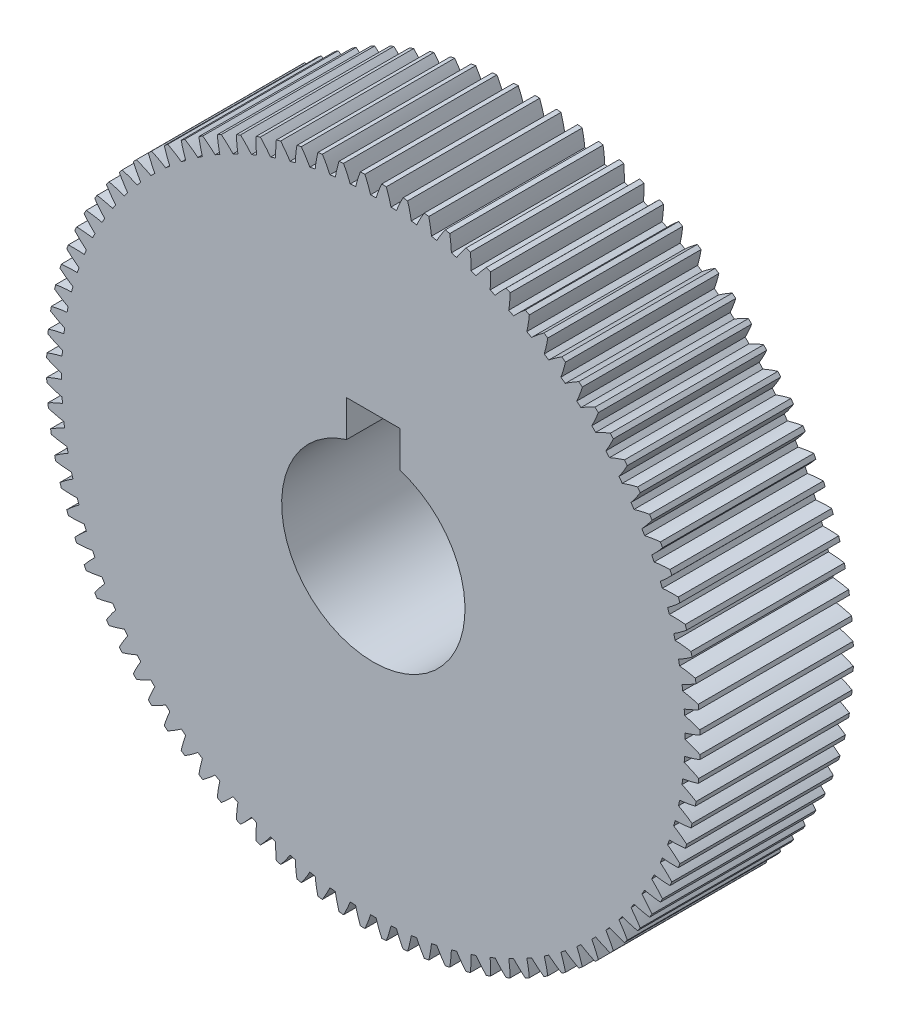
SolidWorks part; units mm, degrees
ref_plane "前视基准面" through (0, 0, 0) normal (0, 0, 1) x (1, 0, 0)
ref_plane "上视基准面" through (0, 0, 0) normal (0, 1, 0) x (1, 0, 0)
ref_plane "右视基准面" through (0, 0, 0) normal (1, 0, 0) x (0, 0, -1)
sketch "Model" plane through (0, 0, 0) normal (0, 0, 1) x (1, 0, 0)
  line L0 (6, 19.0788) -> (6, 23.3)
  line L1 (-6, 23.3) -> (-6, 19.0788)
  line L2 (6, 23.3) -> (-6, 23.3)
  arc A0 (-97.9675, 2.5241) -> (-93.4954, 0.8163) centre (-82.0589, 37.4737) ccw
  arc A1 (-93.4954, 0.8163) -> (-93.4954, -0.8163) centre (0, 0) ccw
  arc A2 (-93.4954, -0.8163) -> (-97.9675, -2.5241) centre (-82.0589, -37.4737) ccw
  arc A3 (-97.9675, -2.5241) -> (-97.9228, -3.8887) centre (0, 0) ccw
  arc A4 (-97.9228, -3.8887) -> (-93.3486, -5.3003) centre (-84.3341, 32.0266) ccw
  arc A5 (-93.3486, -5.3003) -> (-93.2419, -6.9294) centre (0, 0) ccw
  arc A6 (-93.2419, -6.9294) -> (-97.5927, -8.9261) centre (-79.4323, -42.7604) ccw
  arc A7 (-97.5927, -8.9261) -> (-97.4588, -10.2848) centre (0, 0) ccw
  arc A8 (-97.4588, -10.2848) -> (-92.8021, -11.3943) centre (-86.2481, 26.4423) ccw
  arc A9 (-92.8021, -11.3943) -> (-92.589, -13.0129) centre (0, 0) ccw
  arc A10 (-92.589, -13.0129) -> (-96.7999, -15.2898) centre (-76.4655, -47.8639) ccw
  arc A11 (-96.7999, -15.2898) -> (-96.5775, -16.6369) centre (0, 0) ccw
  arc A12 (-96.5775, -16.6369) -> (-91.8582, -17.4394) centre (-87.7929, 20.7448) ccw
  arc A13 (-91.8582, -17.4394) -> (-91.5397, -19.0407) centre (0, 0) ccw
  arc A14 (-91.5397, -19.0407) -> (-95.5926, -21.5881) centre (-73.1714, -52.7625) ccw
  arc A15 (-95.5926, -21.5881) -> (-95.2826, -22.9178) centre (0, 0) ccw
  arc A16 (-95.2826, -22.9178) -> (-90.5209, -23.4099) centre (-88.9617, 14.9584) ccw
  arc A17 (-90.5209, -23.4099) -> (-90.0984, -24.9869) centre (0, 0) ccw
  arc A18 (-90.0984, -24.9869) -> (-93.976, -27.7939) centre (-69.5639, -57.4352) ccw
  arc A19 (-93.976, -27.7939) -> (-93.5797, -29.1005) centre (0, 0) ccw
  arc A20 (-93.5797, -29.1005) -> (-88.796, -29.2801) centre (-89.7495, 9.108) ccw
  arc A21 (-88.796, -29.2801) -> (-88.2713, -30.8261) centre (0, 0) ccw
  arc A22 (-88.2713, -30.8261) -> (-91.957, -33.8808) centre (-65.6585, -61.8619) ccw
  arc A23 (-91.957, -33.8808) -> (-91.4761, -35.1586) centre (0, 0) ccw
  arc A24 (-91.4761, -35.1586) -> (-86.6909, -35.025) centre (-90.1531, 3.2186) ccw
  arc A25 (-86.6909, -35.025) -> (-86.0661, -36.5333) centre (0, 0) ccw
  arc A26 (-86.0661, -36.5333) -> (-89.5442, -39.8225) centre (-61.4719, -66.0237) ccw
  arc A27 (-89.5442, -39.8225) -> (-88.9807, -41.0661) centre (0, 0) ccw
  arc A28 (-88.9807, -41.0661) -> (-84.2145, -40.6199) centre (-90.1705, -2.6846) ccw
  arc A29 (-84.2145, -40.6199) -> (-83.4925, -42.0841) centre (0, 0) ccw
  arc A30 (-83.4925, -42.0841) -> (-86.748, -45.5937) centre (-57.0222, -69.9028) ccw
  arc A31 (-86.748, -45.5937) -> (-86.1044, -46.7978) centre (0, 0) ccw
  arc A32 (-86.1044, -46.7978) -> (-81.3776, -46.0408) centre (-89.8019, -8.5763) ccw
  arc A33 (-81.3776, -46.0408) -> (-80.5613, -47.4547) centre (0, 0) ccw
  arc A34 (-80.5613, -47.4547) -> (-83.5803, -51.1697) centre (-52.3282, -73.4826) ccw
  arc A35 (-83.5803, -51.1697) -> (-82.8593, -52.3291) centre (0, 0) ccw
  arc A36 (-82.8593, -52.3291) -> (-78.1921, -51.2646) centre (-89.0487, -14.4312) ccw
  arc A37 (-78.1921, -51.2646) -> (-77.2851, -52.622) centre (0, 0) ccw
  arc A38 (-77.2851, -52.622) -> (-80.0547, -56.5265) centre (-47.4102, -76.7477) ccw
  arc A39 (-80.0547, -56.5265) -> (-79.2594, -57.6363) centre (0, 0) ccw
  arc A40 (-79.2594, -57.6363) -> (-74.6719, -56.2688) centre (-87.9142, -20.2244) ccw
  arc A41 (-74.6719, -56.2688) -> (-73.678, -57.564) centre (0, 0) ccw
  arc A42 (-73.678, -57.564) -> (-76.1863, -61.6413) centre (-42.2891, -79.6841) ccw
  arc A43 (-76.1863, -61.6413) -> (-75.3201, -62.6967) centre (0, 0) ccw
  arc A44 (-75.3201, -62.6967) -> (-70.8318, -61.0321) centre (-86.4032, -25.9309) ccw
  arc A45 (-70.8318, -61.0321) -> (-69.7554, -62.2596) centre (0, 0) ccw
  arc A46 (-69.7554, -62.2596) -> (-71.9916, -66.4922) centre (-36.987, -82.2794) ccw
  arc A47 (-71.9916, -66.4922) -> (-71.0583, -67.4887) centre (0, 0) ccw
  arc A48 (-71.0583, -67.4887) -> (-66.6885, -65.534) centre (-84.5223, -31.5265) ccw
  arc A49 (-66.6885, -65.534) -> (-65.534, -66.6885) centre (0, 0) ccw
  arc A50 (-65.534, -66.6885) -> (-67.4887, -71.0583) centre (-31.5265, -84.5223) ccw
  arc A51 (-67.4887, -71.0583) -> (-66.4922, -71.9916) centre (0, 0) ccw
  arc A52 (-66.4922, -71.9916) -> (-62.2596, -69.7554) centre (-82.2794, -36.987) ccw
  arc A53 (-62.2596, -69.7554) -> (-61.0321, -70.8318) centre (0, 0) ccw
  arc A54 (-61.0321, -70.8318) -> (-62.6967, -75.3201) centre (-25.9309, -86.4032) ccw
  arc A55 (-62.6967, -75.3201) -> (-61.6413, -76.1863) centre (0, 0) ccw
  arc A56 (-61.6413, -76.1863) -> (-57.564, -73.678) centre (-79.6841, -42.2891) ccw
  arc A57 (-57.564, -73.678) -> (-56.2688, -74.6719) centre (0, 0) ccw
  arc A58 (-56.2688, -74.6719) -> (-57.6363, -79.2594) centre (-20.2244, -87.9142) ccw
  arc A59 (-57.6363, -79.2594) -> (-56.5265, -80.0547) centre (0, 0) ccw
  arc A60 (-56.5265, -80.0547) -> (-52.622, -77.2851) centre (-76.7477, -47.4102) ccw
  arc A61 (-52.622, -77.2851) -> (-51.2646, -78.1921) centre (0, 0) ccw
  arc A62 (-51.2646, -78.1921) -> (-52.3291, -82.8593) centre (-14.4312, -89.0487) ccw
  arc A63 (-52.3291, -82.8593) -> (-51.1697, -83.5803) centre (0, 0) ccw
  arc A64 (-51.1697, -83.5803) -> (-47.4547, -80.5613) centre (-73.4826, -52.3282) ccw
  arc A65 (-47.4547, -80.5613) -> (-46.0408, -81.3776) centre (0, 0) ccw
  arc A66 (-46.0408, -81.3776) -> (-46.7978, -86.1044) centre (-8.5763, -89.8019) ccw
  arc A67 (-46.7978, -86.1044) -> (-45.5937, -86.748) centre (0, 0) ccw
  arc A68 (-45.5937, -86.748) -> (-42.0841, -83.4925) centre (-69.9028, -57.0222) ccw
  arc A69 (-42.0841, -83.4925) -> (-40.6199, -84.2145) centre (0, 0) ccw
  arc A70 (-40.6199, -84.2145) -> (-41.0661, -88.9807) centre (-2.6846, -90.1705) ccw
  arc A71 (-41.0661, -88.9807) -> (-39.8225, -89.5442) centre (0, 0) ccw
  arc A72 (-39.8225, -89.5442) -> (-36.5333, -86.0661) centre (-66.0237, -61.4719) ccw
  arc A73 (-36.5333, -86.0661) -> (-35.025, -86.6909) centre (0, 0) ccw
  arc A74 (-35.025, -86.6909) -> (-35.1586, -91.4761) centre (3.2186, -90.1531) ccw
  arc A75 (-35.1586, -91.4761) -> (-33.8808, -91.957) centre (0, 0) ccw
  arc A76 (-33.8808, -91.957) -> (-30.8261, -88.2713) centre (-61.8619, -65.6585) ccw
  arc A77 (-30.8261, -88.2713) -> (-29.2801, -88.796) centre (0, 0) ccw
  arc A78 (-29.2801, -88.796) -> (-29.1005, -93.5797) centre (9.108, -89.7495) ccw
  arc A79 (-29.1005, -93.5797) -> (-27.7939, -93.976) centre (0, 0) ccw
  arc A80 (-27.7939, -93.976) -> (-24.9869, -90.0984) centre (-57.4352, -69.5639) ccw
  arc A81 (-24.9869, -90.0984) -> (-23.4099, -90.5209) centre (0, 0) ccw
  arc A82 (-23.4099, -90.5209) -> (-22.9178, -95.2826) centre (14.9584, -88.9617) ccw
  arc A83 (-22.9178, -95.2826) -> (-21.5881, -95.5926) centre (0, 0) ccw
  arc A84 (-21.5881, -95.5926) -> (-19.0407, -91.5397) centre (-52.7625, -73.1714) ccw
  arc A85 (-19.0407, -91.5397) -> (-17.4394, -91.8582) centre (0, 0) ccw
  arc A86 (-17.4394, -91.8582) -> (-16.6369, -96.5775) centre (20.7448, -87.7929) ccw
  arc A87 (-16.6369, -96.5775) -> (-15.2898, -96.7999) centre (0, 0) ccw
  arc A88 (-15.2898, -96.7999) -> (-13.0129, -92.589) centre (-47.8639, -76.4655) ccw
  arc A89 (-13.0129, -92.589) -> (-11.3943, -92.8021) centre (0, 0) ccw
  arc A90 (-11.3943, -92.8021) -> (-10.2848, -97.4588) centre (26.4423, -86.2481) ccw
  arc A91 (-10.2848, -97.4588) -> (-8.9261, -97.5927) centre (0, 0) ccw
  arc A92 (-8.9261, -97.5927) -> (-6.9294, -93.2419) centre (-42.7604, -79.4323) ccw
  arc A93 (-6.9294, -93.2419) -> (-5.3003, -93.3486) centre (0, 0) ccw
  arc A94 (-5.3003, -93.3486) -> (-3.8887, -97.9228) centre (32.0266, -84.3341) ccw
  arc A95 (-3.8887, -97.9228) -> (-2.5241, -97.9675) centre (0, 0) ccw
  arc A96 (-2.5241, -97.9675) -> (-0.8163, -93.4954) centre (-37.4737, -82.0589) ccw
  arc A97 (-0.8163, -93.4954) -> (0.8163, -93.4954) centre (0, 0) ccw
  arc A98 (0.8163, -93.4954) -> (2.5241, -97.9675) centre (37.4737, -82.0589) ccw
  arc A99 (2.5241, -97.9675) -> (3.8887, -97.9228) centre (0, 0) ccw
  arc A100 (3.8887, -97.9228) -> (5.3003, -93.3486) centre (-32.0266, -84.3341) ccw
  arc A101 (5.3003, -93.3486) -> (6.9294, -93.2419) centre (0, 0) ccw
  arc A102 (6.9294, -93.2419) -> (8.9261, -97.5927) centre (42.7604, -79.4323) ccw
  arc A103 (8.9261, -97.5927) -> (10.2848, -97.4588) centre (0, 0) ccw
  arc A104 (10.2848, -97.4588) -> (11.3943, -92.8021) centre (-26.4423, -86.2481) ccw
  arc A105 (11.3943, -92.8021) -> (13.0129, -92.589) centre (0, 0) ccw
  arc A106 (13.0129, -92.589) -> (15.2898, -96.7999) centre (47.8639, -76.4655) ccw
  arc A107 (15.2898, -96.7999) -> (16.6369, -96.5775) centre (0, 0) ccw
  arc A108 (16.6369, -96.5775) -> (17.4394, -91.8582) centre (-20.7448, -87.7929) ccw
  arc A109 (17.4394, -91.8582) -> (19.0407, -91.5397) centre (0, 0) ccw
  arc A110 (19.0407, -91.5397) -> (21.5881, -95.5926) centre (52.7625, -73.1714) ccw
  arc A111 (21.5881, -95.5926) -> (22.9178, -95.2826) centre (0, 0) ccw
  arc A112 (22.9178, -95.2826) -> (23.4099, -90.5209) centre (-14.9584, -88.9617) ccw
  arc A113 (23.4099, -90.5209) -> (24.9869, -90.0984) centre (0, 0) ccw
  arc A114 (24.9869, -90.0984) -> (27.7939, -93.976) centre (57.4352, -69.5639) ccw
  arc A115 (27.7939, -93.976) -> (29.1005, -93.5797) centre (0, 0) ccw
  arc A116 (29.1005, -93.5797) -> (29.2801, -88.796) centre (-9.108, -89.7495) ccw
  arc A117 (29.2801, -88.796) -> (30.8261, -88.2713) centre (0, 0) ccw
  arc A118 (30.8261, -88.2713) -> (33.8808, -91.957) centre (61.8619, -65.6585) ccw
  arc A119 (33.8808, -91.957) -> (35.1586, -91.4761) centre (0, 0) ccw
  arc A120 (35.1586, -91.4761) -> (35.025, -86.6909) centre (-3.2186, -90.1531) ccw
  arc A121 (35.025, -86.6909) -> (36.5333, -86.0661) centre (0, 0) ccw
  arc A122 (36.5333, -86.0661) -> (39.8225, -89.5442) centre (66.0237, -61.4719) ccw
  arc A123 (39.8225, -89.5442) -> (41.0661, -88.9807) centre (0, 0) ccw
  arc A124 (41.0661, -88.9807) -> (40.6199, -84.2145) centre (2.6846, -90.1705) ccw
  arc A125 (40.6199, -84.2145) -> (42.0841, -83.4925) centre (0, 0) ccw
  arc A126 (42.0841, -83.4925) -> (45.5937, -86.748) centre (69.9028, -57.0222) ccw
  arc A127 (45.5937, -86.748) -> (46.7978, -86.1044) centre (0, 0) ccw
  arc A128 (46.7978, -86.1044) -> (46.0408, -81.3776) centre (8.5763, -89.8019) ccw
  arc A129 (46.0408, -81.3776) -> (47.4547, -80.5613) centre (0, 0) ccw
  arc A130 (47.4547, -80.5613) -> (51.1697, -83.5803) centre (73.4826, -52.3282) ccw
  arc A131 (51.1697, -83.5803) -> (52.3291, -82.8593) centre (0, 0) ccw
  arc A132 (52.3291, -82.8593) -> (51.2646, -78.1921) centre (14.4312, -89.0487) ccw
  arc A133 (51.2646, -78.1921) -> (52.622, -77.2851) centre (0, 0) ccw
  arc A134 (52.622, -77.2851) -> (56.5265, -80.0547) centre (76.7477, -47.4102) ccw
  arc A135 (56.5265, -80.0547) -> (57.6363, -79.2594) centre (0, 0) ccw
  arc A136 (57.6363, -79.2594) -> (56.2688, -74.6719) centre (20.2244, -87.9142) ccw
  arc A137 (56.2688, -74.6719) -> (57.564, -73.678) centre (0, 0) ccw
  arc A138 (57.564, -73.678) -> (61.6413, -76.1863) centre (79.6841, -42.2891) ccw
  arc A139 (61.6413, -76.1863) -> (62.6967, -75.3201) centre (0, 0) ccw
  arc A140 (62.6967, -75.3201) -> (61.0321, -70.8318) centre (25.9309, -86.4032) ccw
  arc A141 (61.0321, -70.8318) -> (62.2596, -69.7554) centre (0, 0) ccw
  arc A142 (62.2596, -69.7554) -> (66.4922, -71.9916) centre (82.2794, -36.987) ccw
  arc A143 (66.4922, -71.9916) -> (67.4887, -71.0583) centre (0, 0) ccw
  arc A144 (67.4887, -71.0583) -> (65.534, -66.6885) centre (31.5265, -84.5223) ccw
  arc A145 (65.534, -66.6885) -> (66.6885, -65.534) centre (0, 0) ccw
  arc A146 (66.6885, -65.534) -> (71.0583, -67.4887) centre (84.5223, -31.5265) ccw
  arc A147 (71.0583, -67.4887) -> (71.9916, -66.4922) centre (0, 0) ccw
  arc A148 (71.9916, -66.4922) -> (69.7554, -62.2596) centre (36.987, -82.2794) ccw
  arc A149 (69.7554, -62.2596) -> (70.8318, -61.0321) centre (0, 0) ccw
  arc A150 (70.8318, -61.0321) -> (75.3201, -62.6967) centre (86.4032, -25.9309) ccw
  arc A151 (75.3201, -62.6967) -> (76.1863, -61.6413) centre (0, 0) ccw
  arc A152 (76.1863, -61.6413) -> (73.678, -57.564) centre (42.2891, -79.6841) ccw
  arc A153 (73.678, -57.564) -> (74.6719, -56.2688) centre (0, 0) ccw
  arc A154 (74.6719, -56.2688) -> (79.2594, -57.6363) centre (87.9142, -20.2244) ccw
  arc A155 (79.2594, -57.6363) -> (80.0547, -56.5265) centre (0, 0) ccw
  arc A156 (80.0547, -56.5265) -> (77.2851, -52.622) centre (47.4102, -76.7477) ccw
  arc A157 (77.2851, -52.622) -> (78.1921, -51.2646) centre (0, 0) ccw
  arc A158 (78.1921, -51.2646) -> (82.8593, -52.3291) centre (89.0487, -14.4312) ccw
  arc A159 (82.8593, -52.3291) -> (83.5803, -51.1697) centre (0, 0) ccw
  arc A160 (83.5803, -51.1697) -> (80.5613, -47.4547) centre (52.3282, -73.4826) ccw
  arc A161 (80.5613, -47.4547) -> (81.3776, -46.0408) centre (0, 0) ccw
  arc A162 (81.3776, -46.0408) -> (86.1044, -46.7978) centre (89.8019, -8.5763) ccw
  arc A163 (86.1044, -46.7978) -> (86.748, -45.5937) centre (0, 0) ccw
  arc A164 (86.748, -45.5937) -> (83.4925, -42.0841) centre (57.0222, -69.9028) ccw
  arc A165 (83.4925, -42.0841) -> (84.2145, -40.6199) centre (0, 0) ccw
  arc A166 (84.2145, -40.6199) -> (88.9807, -41.0661) centre (90.1705, -2.6846) ccw
  arc A167 (88.9807, -41.0661) -> (89.5442, -39.8225) centre (0, 0) ccw
  arc A168 (89.5442, -39.8225) -> (86.0661, -36.5333) centre (61.4719, -66.0237) ccw
  arc A169 (86.0661, -36.5333) -> (86.6909, -35.025) centre (0, 0) ccw
  arc A170 (86.6909, -35.025) -> (91.4761, -35.1586) centre (90.1531, 3.2186) ccw
  arc A171 (91.4761, -35.1586) -> (91.957, -33.8808) centre (0, 0) ccw
  arc A172 (91.957, -33.8808) -> (88.2713, -30.8261) centre (65.6585, -61.8619) ccw
  arc A173 (88.2713, -30.8261) -> (88.796, -29.2801) centre (0, 0) ccw
  arc A174 (88.796, -29.2801) -> (93.5797, -29.1005) centre (89.7495, 9.108) ccw
  arc A175 (93.5797, -29.1005) -> (93.976, -27.7939) centre (0, 0) ccw
  arc A176 (93.976, -27.7939) -> (90.0984, -24.9869) centre (69.5639, -57.4352) ccw
  arc A177 (90.0984, -24.9869) -> (90.5209, -23.4099) centre (0, 0) ccw
  arc A178 (90.5209, -23.4099) -> (95.2826, -22.9178) centre (88.9617, 14.9584) ccw
  arc A179 (95.2826, -22.9178) -> (95.5926, -21.5881) centre (0, 0) ccw
  arc A180 (95.5926, -21.5881) -> (91.5397, -19.0407) centre (73.1714, -52.7625) ccw
  arc A181 (91.5397, -19.0407) -> (91.8582, -17.4394) centre (0, 0) ccw
  arc A182 (91.8582, -17.4394) -> (96.5775, -16.6369) centre (87.7929, 20.7448) ccw
  arc A183 (96.5775, -16.6369) -> (96.7999, -15.2898) centre (0, 0) ccw
  arc A184 (96.7999, -15.2898) -> (92.589, -13.0129) centre (76.4655, -47.8639) ccw
  arc A185 (92.589, -13.0129) -> (92.8021, -11.3943) centre (0, 0) ccw
  arc A186 (92.8021, -11.3943) -> (97.4588, -10.2848) centre (86.2481, 26.4423) ccw
  arc A187 (97.4588, -10.2848) -> (97.5927, -8.9261) centre (0, 0) ccw
  arc A188 (97.5927, -8.9261) -> (93.2419, -6.9294) centre (79.4323, -42.7604) ccw
  arc A189 (93.2419, -6.9294) -> (93.3486, -5.3003) centre (0, 0) ccw
  arc A190 (93.3486, -5.3003) -> (97.9228, -3.8887) centre (84.3341, 32.0266) ccw
  arc A191 (97.9228, -3.8887) -> (97.9675, -2.5241) centre (0, 0) ccw
  arc A192 (97.9675, -2.5241) -> (93.4954, -0.8163) centre (82.0589, -37.4737) ccw
  arc A193 (93.4954, -0.8163) -> (93.4954, 0.8163) centre (0, 0) ccw
  arc A194 (93.4954, 0.8163) -> (97.9675, 2.5241) centre (82.0589, 37.4737) ccw
  arc A195 (97.9675, 2.5241) -> (97.9228, 3.8887) centre (0, 0) ccw
  arc A196 (97.9228, 3.8887) -> (93.3486, 5.3003) centre (84.3341, -32.0266) ccw
  arc A197 (93.3486, 5.3003) -> (93.2419, 6.9294) centre (0, 0) ccw
  arc A198 (93.2419, 6.9294) -> (97.5927, 8.9261) centre (79.4323, 42.7604) ccw
  arc A199 (97.5927, 8.9261) -> (97.4588, 10.2848) centre (0, 0) ccw
  arc A200 (97.4588, 10.2848) -> (92.8021, 11.3943) centre (86.2481, -26.4423) ccw
  arc A201 (92.8021, 11.3943) -> (92.589, 13.0129) centre (0, 0) ccw
  arc A202 (92.589, 13.0129) -> (96.7999, 15.2898) centre (76.4655, 47.8639) ccw
  arc A203 (96.7999, 15.2898) -> (96.5775, 16.6369) centre (0, 0) ccw
  arc A204 (96.5775, 16.6369) -> (91.8582, 17.4394) centre (87.7929, -20.7448) ccw
  arc A205 (91.8582, 17.4394) -> (91.5397, 19.0407) centre (0, 0) ccw
  arc A206 (91.5397, 19.0407) -> (95.5926, 21.5881) centre (73.1714, 52.7625) ccw
  arc A207 (95.5926, 21.5881) -> (95.2826, 22.9178) centre (0, 0) ccw
  arc A208 (95.2826, 22.9178) -> (90.5209, 23.4099) centre (88.9617, -14.9584) ccw
  arc A209 (90.5209, 23.4099) -> (90.0984, 24.9869) centre (0, 0) ccw
  arc A210 (90.0984, 24.9869) -> (93.976, 27.7939) centre (69.5639, 57.4352) ccw
  arc A211 (93.976, 27.7939) -> (93.5797, 29.1005) centre (0, 0) ccw
  arc A212 (93.5797, 29.1005) -> (88.796, 29.2801) centre (89.7495, -9.108) ccw
  arc A213 (88.796, 29.2801) -> (88.2713, 30.8261) centre (0, 0) ccw
  arc A214 (88.2713, 30.8261) -> (91.957, 33.8808) centre (65.6585, 61.8619) ccw
  arc A215 (91.957, 33.8808) -> (91.4761, 35.1586) centre (0, 0) ccw
  arc A216 (91.4761, 35.1586) -> (86.6909, 35.025) centre (90.1531, -3.2186) ccw
  arc A217 (86.6909, 35.025) -> (86.0661, 36.5333) centre (0, 0) ccw
  arc A218 (86.0661, 36.5333) -> (89.5442, 39.8225) centre (61.4719, 66.0237) ccw
  arc A219 (89.5442, 39.8225) -> (88.9807, 41.0661) centre (0, 0) ccw
  arc A220 (88.9807, 41.0661) -> (84.2145, 40.6199) centre (90.1705, 2.6846) ccw
  arc A221 (84.2145, 40.6199) -> (83.4925, 42.0841) centre (0, 0) ccw
  arc A222 (83.4925, 42.0841) -> (86.748, 45.5937) centre (57.0222, 69.9028) ccw
  arc A223 (86.748, 45.5937) -> (86.1044, 46.7978) centre (0, 0) ccw
  arc A224 (86.1044, 46.7978) -> (81.3776, 46.0408) centre (89.8019, 8.5763) ccw
  arc A225 (81.3776, 46.0408) -> (80.5613, 47.4547) centre (0, 0) ccw
  arc A226 (80.5613, 47.4547) -> (83.5803, 51.1697) centre (52.3282, 73.4826) ccw
  arc A227 (83.5803, 51.1697) -> (82.8593, 52.3291) centre (0, 0) ccw
  arc A228 (82.8593, 52.3291) -> (78.1921, 51.2646) centre (89.0487, 14.4312) ccw
  arc A229 (78.1921, 51.2646) -> (77.2851, 52.622) centre (0, 0) ccw
  arc A230 (77.2851, 52.622) -> (80.0547, 56.5265) centre (47.4102, 76.7477) ccw
  arc A231 (80.0547, 56.5265) -> (79.2594, 57.6363) centre (0, 0) ccw
  arc A232 (79.2594, 57.6363) -> (74.6719, 56.2688) centre (87.9142, 20.2244) ccw
  arc A233 (74.6719, 56.2688) -> (73.678, 57.564) centre (0, 0) ccw
  arc A234 (73.678, 57.564) -> (76.1863, 61.6413) centre (42.2891, 79.6841) ccw
  arc A235 (76.1863, 61.6413) -> (75.3201, 62.6967) centre (0, 0) ccw
  arc A236 (75.3201, 62.6967) -> (70.8318, 61.0321) centre (86.4032, 25.9309) ccw
  arc A237 (70.8318, 61.0321) -> (69.7554, 62.2596) centre (0, 0) ccw
  arc A238 (69.7554, 62.2596) -> (71.9916, 66.4922) centre (36.987, 82.2794) ccw
  arc A239 (71.9916, 66.4922) -> (71.0583, 67.4887) centre (0, 0) ccw
  arc A240 (71.0583, 67.4887) -> (66.6885, 65.534) centre (84.5223, 31.5265) ccw
  arc A241 (66.6885, 65.534) -> (65.534, 66.6885) centre (0, 0) ccw
  arc A242 (65.534, 66.6885) -> (67.4887, 71.0583) centre (31.5265, 84.5223) ccw
  arc A243 (67.4887, 71.0583) -> (66.4922, 71.9916) centre (0, 0) ccw
  arc A244 (66.4922, 71.9916) -> (62.2596, 69.7554) centre (82.2794, 36.987) ccw
  arc A245 (62.2596, 69.7554) -> (61.0321, 70.8318) centre (0, 0) ccw
  arc A246 (61.0321, 70.8318) -> (62.6967, 75.3201) centre (25.9309, 86.4032) ccw
  arc A247 (62.6967, 75.3201) -> (61.6413, 76.1863) centre (0, 0) ccw
  arc A248 (61.6413, 76.1863) -> (57.564, 73.678) centre (79.6841, 42.2891) ccw
  arc A249 (57.564, 73.678) -> (56.2688, 74.6719) centre (0, 0) ccw
  arc A250 (56.2688, 74.6719) -> (57.6363, 79.2594) centre (20.2244, 87.9142) ccw
  arc A251 (57.6363, 79.2594) -> (56.5265, 80.0547) centre (0, 0) ccw
  arc A252 (56.5265, 80.0547) -> (52.622, 77.2851) centre (76.7477, 47.4102) ccw
  arc A253 (52.622, 77.2851) -> (51.2646, 78.1921) centre (0, 0) ccw
  arc A254 (51.2646, 78.1921) -> (52.3291, 82.8593) centre (14.4312, 89.0487) ccw
  arc A255 (52.3291, 82.8593) -> (51.1697, 83.5803) centre (0, 0) ccw
  arc A256 (51.1697, 83.5803) -> (47.4547, 80.5613) centre (73.4826, 52.3282) ccw
  arc A257 (47.4547, 80.5613) -> (46.0408, 81.3776) centre (0, 0) ccw
  arc A258 (46.0408, 81.3776) -> (46.7978, 86.1044) centre (8.5763, 89.8019) ccw
  arc A259 (46.7978, 86.1044) -> (45.5937, 86.748) centre (0, 0) ccw
  arc A260 (45.5937, 86.748) -> (42.0841, 83.4925) centre (69.9028, 57.0222) ccw
  arc A261 (42.0841, 83.4925) -> (40.6199, 84.2145) centre (0, 0) ccw
  arc A262 (40.6199, 84.2145) -> (41.0661, 88.9807) centre (2.6846, 90.1705) ccw
  arc A263 (41.0661, 88.9807) -> (39.8225, 89.5442) centre (0, 0) ccw
  arc A264 (39.8225, 89.5442) -> (36.5333, 86.0661) centre (66.0237, 61.4719) ccw
  arc A265 (36.5333, 86.0661) -> (35.025, 86.6909) centre (0, 0) ccw
  arc A266 (35.025, 86.6909) -> (35.1586, 91.4761) centre (-3.2186, 90.1531) ccw
  arc A267 (35.1586, 91.4761) -> (33.8808, 91.957) centre (0, 0) ccw
  arc A268 (33.8808, 91.957) -> (30.8261, 88.2713) centre (61.8619, 65.6585) ccw
  arc A269 (30.8261, 88.2713) -> (29.2801, 88.796) centre (0, 0) ccw
  arc A270 (29.2801, 88.796) -> (29.1005, 93.5797) centre (-9.108, 89.7495) ccw
  arc A271 (29.1005, 93.5797) -> (27.7939, 93.976) centre (0, 0) ccw
  arc A272 (27.7939, 93.976) -> (24.9869, 90.0984) centre (57.4352, 69.5639) ccw
  arc A273 (24.9869, 90.0984) -> (23.4099, 90.5209) centre (0, 0) ccw
  arc A274 (23.4099, 90.5209) -> (22.9178, 95.2826) centre (-14.9584, 88.9617) ccw
  arc A275 (22.9178, 95.2826) -> (21.5881, 95.5926) centre (0, 0) ccw
  arc A276 (21.5881, 95.5926) -> (19.0407, 91.5397) centre (52.7625, 73.1714) ccw
  arc A277 (19.0407, 91.5397) -> (17.4394, 91.8582) centre (0, 0) ccw
  arc A278 (17.4394, 91.8582) -> (16.6369, 96.5775) centre (-20.7448, 87.7929) ccw
  arc A279 (16.6369, 96.5775) -> (15.2898, 96.7999) centre (0, 0) ccw
  arc A280 (15.2898, 96.7999) -> (13.0129, 92.589) centre (47.8639, 76.4655) ccw
  arc A281 (13.0129, 92.589) -> (11.3943, 92.8021) centre (0, 0) ccw
  arc A282 (11.3943, 92.8021) -> (10.2848, 97.4588) centre (-26.4423, 86.2481) ccw
  arc A283 (10.2848, 97.4588) -> (8.9261, 97.5927) centre (0, 0) ccw
  arc A284 (8.9261, 97.5927) -> (6.9294, 93.2419) centre (42.7604, 79.4323) ccw
  arc A285 (6.9294, 93.2419) -> (5.3003, 93.3486) centre (0, 0) ccw
  arc A286 (5.3003, 93.3486) -> (3.8887, 97.9228) centre (-32.0266, 84.3341) ccw
  arc A287 (3.8887, 97.9228) -> (2.5241, 97.9675) centre (0, 0) ccw
  arc A288 (2.5241, 97.9675) -> (0.8163, 93.4954) centre (37.4737, 82.0589) ccw
  arc A289 (0.8163, 93.4954) -> (-0.8163, 93.4954) centre (0, 0) ccw
  arc A290 (-0.8163, 93.4954) -> (-2.5241, 97.9675) centre (-37.4737, 82.0589) ccw
  arc A291 (-2.5241, 97.9675) -> (-3.8887, 97.9228) centre (0, 0) ccw
  arc A292 (-3.8887, 97.9228) -> (-5.3003, 93.3486) centre (32.0266, 84.3341) ccw
  arc A293 (-5.3003, 93.3486) -> (-6.9294, 93.2419) centre (0, 0) ccw
  arc A294 (-6.9294, 93.2419) -> (-8.9261, 97.5927) centre (-42.7604, 79.4323) ccw
  arc A295 (-8.9261, 97.5927) -> (-10.2848, 97.4588) centre (0, 0) ccw
  arc A296 (-10.2848, 97.4588) -> (-11.3943, 92.8021) centre (26.4423, 86.2481) ccw
  arc A297 (-11.3943, 92.8021) -> (-13.0129, 92.589) centre (0, 0) ccw
  arc A298 (-13.0129, 92.589) -> (-15.2898, 96.7999) centre (-47.8639, 76.4655) ccw
  arc A299 (-15.2898, 96.7999) -> (-16.6369, 96.5775) centre (0, 0) ccw
  arc A300 (-16.6369, 96.5775) -> (-17.4394, 91.8582) centre (20.7448, 87.7929) ccw
  arc A301 (-17.4394, 91.8582) -> (-19.0407, 91.5397) centre (0, 0) ccw
  arc A302 (-19.0407, 91.5397) -> (-21.5881, 95.5926) centre (-52.7625, 73.1714) ccw
  arc A303 (-21.5881, 95.5926) -> (-22.9178, 95.2826) centre (0, 0) ccw
  arc A304 (-22.9178, 95.2826) -> (-23.4099, 90.5209) centre (14.9584, 88.9617) ccw
  arc A305 (-23.4099, 90.5209) -> (-24.9869, 90.0984) centre (0, 0) ccw
  arc A306 (-24.9869, 90.0984) -> (-27.7939, 93.976) centre (-57.4352, 69.5639) ccw
  arc A307 (-27.7939, 93.976) -> (-29.1005, 93.5797) centre (0, 0) ccw
  arc A308 (-29.1005, 93.5797) -> (-29.2801, 88.796) centre (9.108, 89.7495) ccw
  arc A309 (-29.2801, 88.796) -> (-30.8261, 88.2713) centre (0, 0) ccw
  arc A310 (-30.8261, 88.2713) -> (-33.8808, 91.957) centre (-61.8619, 65.6585) ccw
  arc A311 (-33.8808, 91.957) -> (-35.1586, 91.4761) centre (0, 0) ccw
  arc A312 (-35.1586, 91.4761) -> (-35.025, 86.6909) centre (3.2186, 90.1531) ccw
  arc A313 (-35.025, 86.6909) -> (-36.5333, 86.0661) centre (0, 0) ccw
  arc A314 (-36.5333, 86.0661) -> (-39.8225, 89.5442) centre (-66.0237, 61.4719) ccw
  arc A315 (-39.8225, 89.5442) -> (-41.0661, 88.9807) centre (0, 0) ccw
  arc A316 (-41.0661, 88.9807) -> (-40.6199, 84.2145) centre (-2.6846, 90.1705) ccw
  arc A317 (-40.6199, 84.2145) -> (-42.0841, 83.4925) centre (0, 0) ccw
  arc A318 (-42.0841, 83.4925) -> (-45.5937, 86.748) centre (-69.9028, 57.0222) ccw
  arc A319 (-45.5937, 86.748) -> (-46.7978, 86.1044) centre (0, 0) ccw
  arc A320 (-46.7978, 86.1044) -> (-46.0408, 81.3776) centre (-8.5763, 89.8019) ccw
  arc A321 (-46.0408, 81.3776) -> (-47.4547, 80.5613) centre (0, 0) ccw
  arc A322 (-47.4547, 80.5613) -> (-51.1697, 83.5803) centre (-73.4826, 52.3282) ccw
  arc A323 (-51.1697, 83.5803) -> (-52.3291, 82.8593) centre (0, 0) ccw
  arc A324 (-52.3291, 82.8593) -> (-51.2646, 78.1921) centre (-14.4312, 89.0487) ccw
  arc A325 (-51.2646, 78.1921) -> (-52.622, 77.2851) centre (0, 0) ccw
  arc A326 (-52.622, 77.2851) -> (-56.5265, 80.0547) centre (-76.7477, 47.4102) ccw
  arc A327 (-56.5265, 80.0547) -> (-57.6363, 79.2594) centre (0, 0) ccw
  arc A328 (-57.6363, 79.2594) -> (-56.2688, 74.6719) centre (-20.2244, 87.9142) ccw
  arc A329 (-56.2688, 74.6719) -> (-57.564, 73.678) centre (0, 0) ccw
  arc A330 (-57.564, 73.678) -> (-61.6413, 76.1863) centre (-79.6841, 42.2891) ccw
  arc A331 (-61.6413, 76.1863) -> (-62.6967, 75.3201) centre (0, 0) ccw
  arc A332 (-62.6967, 75.3201) -> (-61.0321, 70.8318) centre (-25.9309, 86.4032) ccw
  arc A333 (-61.0321, 70.8318) -> (-62.2596, 69.7554) centre (0, 0) ccw
  arc A334 (-62.2596, 69.7554) -> (-66.4922, 71.9916) centre (-82.2794, 36.987) ccw
  arc A335 (-66.4922, 71.9916) -> (-67.4887, 71.0583) centre (0, 0) ccw
  arc A336 (-67.4887, 71.0583) -> (-65.534, 66.6885) centre (-31.5265, 84.5223) ccw
  arc A337 (-65.534, 66.6885) -> (-66.6885, 65.534) centre (0, 0) ccw
  arc A338 (-66.6885, 65.534) -> (-71.0583, 67.4887) centre (-84.5223, 31.5265) ccw
  arc A339 (-71.0583, 67.4887) -> (-71.9916, 66.4922) centre (0, 0) ccw
  arc A340 (-71.9916, 66.4922) -> (-69.7554, 62.2596) centre (-36.987, 82.2794) ccw
  arc A341 (-69.7554, 62.2596) -> (-70.8318, 61.0321) centre (0, 0) ccw
  arc A342 (-70.8318, 61.0321) -> (-75.3201, 62.6967) centre (-86.4032, 25.9309) ccw
  arc A343 (-75.3201, 62.6967) -> (-76.1863, 61.6413) centre (0, 0) ccw
  arc A344 (-76.1863, 61.6413) -> (-73.678, 57.564) centre (-42.2891, 79.6841) ccw
  arc A345 (-73.678, 57.564) -> (-74.6719, 56.2688) centre (0, 0) ccw
  arc A346 (-74.6719, 56.2688) -> (-79.2594, 57.6363) centre (-87.9142, 20.2244) ccw
  arc A347 (-79.2594, 57.6363) -> (-80.0547, 56.5265) centre (0, 0) ccw
  arc A348 (-80.0547, 56.5265) -> (-77.2851, 52.622) centre (-47.4102, 76.7477) ccw
  arc A349 (-77.2851, 52.622) -> (-78.1921, 51.2646) centre (0, 0) ccw
  arc A350 (-78.1921, 51.2646) -> (-82.8593, 52.3291) centre (-89.0487, 14.4312) ccw
  arc A351 (-82.8593, 52.3291) -> (-83.5803, 51.1697) centre (0, 0) ccw
  arc A352 (-83.5803, 51.1697) -> (-80.5613, 47.4547) centre (-52.3282, 73.4826) ccw
  arc A353 (-80.5613, 47.4547) -> (-81.3776, 46.0408) centre (0, 0) ccw
  arc A354 (-81.3776, 46.0408) -> (-86.1044, 46.7978) centre (-89.8019, 8.5763) ccw
  arc A355 (-86.1044, 46.7978) -> (-86.748, 45.5937) centre (0, 0) ccw
  arc A356 (-86.748, 45.5937) -> (-83.4925, 42.0841) centre (-57.0222, 69.9028) ccw
  arc A357 (-83.4925, 42.0841) -> (-84.2145, 40.6199) centre (0, 0) ccw
  arc A358 (-84.2145, 40.6199) -> (-88.9807, 41.0661) centre (-90.1705, 2.6846) ccw
  arc A359 (-88.9807, 41.0661) -> (-89.5442, 39.8225) centre (0, 0) ccw
  arc A360 (-89.5442, 39.8225) -> (-86.0661, 36.5333) centre (-61.4719, 66.0237) ccw
  arc A361 (-86.0661, 36.5333) -> (-86.6909, 35.025) centre (0, 0) ccw
  arc A362 (-86.6909, 35.025) -> (-91.4761, 35.1586) centre (-90.1531, -3.2186) ccw
  arc A363 (-91.4761, 35.1586) -> (-91.957, 33.8808) centre (0, 0) ccw
  arc A364 (-91.957, 33.8808) -> (-88.2713, 30.8261) centre (-65.6585, 61.8619) ccw
  arc A365 (-88.2713, 30.8261) -> (-88.796, 29.2801) centre (0, 0) ccw
  arc A366 (-88.796, 29.2801) -> (-93.5797, 29.1005) centre (-89.7495, -9.108) ccw
  arc A367 (-93.5797, 29.1005) -> (-93.976, 27.7939) centre (0, 0) ccw
  arc A368 (-93.976, 27.7939) -> (-90.0984, 24.9869) centre (-69.5639, 57.4352) ccw
  arc A369 (-90.0984, 24.9869) -> (-90.5209, 23.4099) centre (0, 0) ccw
  arc A370 (-90.5209, 23.4099) -> (-95.2826, 22.9178) centre (-88.9617, -14.9584) ccw
  arc A371 (-95.2826, 22.9178) -> (-95.5926, 21.5881) centre (0, 0) ccw
  arc A372 (-95.5926, 21.5881) -> (-91.5397, 19.0407) centre (-73.1714, 52.7625) ccw
  arc A373 (-91.5397, 19.0407) -> (-91.8582, 17.4394) centre (0, 0) ccw
  arc A374 (-91.8582, 17.4394) -> (-96.5775, 16.6369) centre (-87.7929, -20.7448) ccw
  arc A375 (-96.5775, 16.6369) -> (-96.7999, 15.2898) centre (0, 0) ccw
  arc A376 (-96.7999, 15.2898) -> (-92.589, 13.0129) centre (-76.4655, 47.8639) ccw
  arc A377 (-92.589, 13.0129) -> (-92.8021, 11.3943) centre (0, 0) ccw
  arc A378 (-92.8021, 11.3943) -> (-97.4588, 10.2848) centre (-86.2481, -26.4423) ccw
  arc A379 (-97.4588, 10.2848) -> (-97.5927, 8.9261) centre (0, 0) ccw
  arc A380 (-97.5927, 8.9261) -> (-93.2419, 6.9294) centre (-79.4323, 42.7604) ccw
  arc A381 (-93.2419, 6.9294) -> (-93.3486, 5.3003) centre (0, 0) ccw
  arc A382 (-93.3486, 5.3003) -> (-97.9228, 3.8887) centre (-84.3341, -32.0266) ccw
  arc A383 (-97.9228, 3.8887) -> (-97.9675, 2.5241) centre (0, 0) ccw
  arc A384 (-6, 19.0788) -> (6, 19.0788) centre (0, 0) ccw
extrude "凸台-拉伸1" add sketch "Model" along normal blind 46
sketch "草图1" plane through (0, 0, 46) normal (0, 0, 1) x (1, 0, 0)
  line L0 (0, 0) -> (0, 37.2)
  line L1 (0, 37.2) -> (-8, 37.2)
  line L2 (0, 37.2) -> (8, 37.2)
  line L3 (-8, 37.2) -> (-8, 26.3106)
  line L4 (8, 37.2) -> (8, 26.3106)
  circle A0 centre (0, 0) radius 27.5
  dimension "D1" = 55
  dimension "D2" = 37.2
  dimension "D3" = 8
  dimension "D4" = 8
extrude "切除-拉伸1" cut sketch "草图1" against normal blind 90 contours A0 L4 L2 L0 | A0 L0 L1 L3 | A0 region at (-4.0782, 32.1473, 46) region at (4.0782, 32.1473, 46) region at (3.9296, 26.4317, 46)
